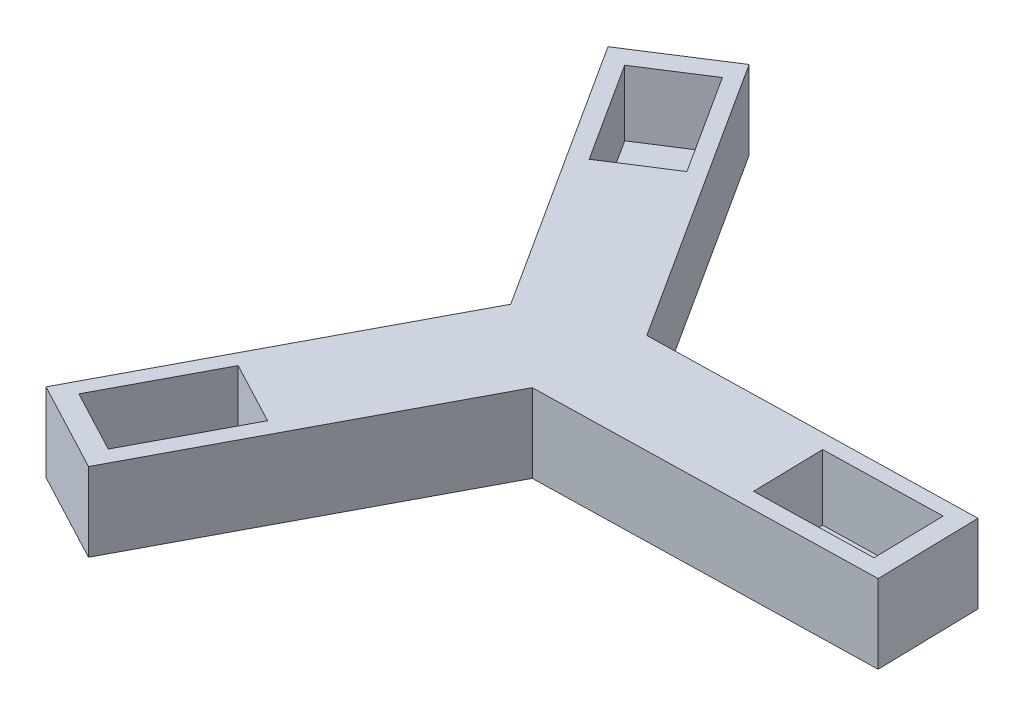
SolidWorks part; units mm, degrees
ref_plane "Front Plane" through (0, 0, 0) normal (0, 0, 1) x (1, 0, 0)
ref_plane "Top Plane" through (0, 0, 0) normal (0, 1, 0) x (1, 0, 0)
ref_plane "Right Plane" through (0, 0, 0) normal (1, 0, 0) x (0, 0, -1)
sketch "Sketch2" plane through (0, 0, 0) normal (0, 1, 0) x (1, 0, 0)
  line L1 (-129.6446, 105.7754) -> (170.3554, 105.7754)
  line L2 (-129.6446, 105.7754) -> (-129.6446, -194.2246)
  line L3 (-129.6446, -194.2246) -> (170.3554, -194.2246)
  line L4 (170.3554, 105.7754) -> (170.3554, -194.2246)
  dimension "D1" = 300
  dimension "D2" = 300
extrude "Boss-Extrude1" add sketch "Sketch2" along normal blind 10
sketch "Sketch7" plane through (0, 10, 0) normal (0, 1, 0) x (1, 0, 0)
  line L0 (-52.501, 16.4051) -> (-76.8122, 54.2728)
  line L1 (-76.8122, 54.2728) -> (-54.0916, 68.8596)
  line L2 (-52.501, 16.4051) -> (-29.7804, 30.9918)
  line L3 (-29.7804, 30.9918) -> (-54.0916, 68.8596)
  line L4 (-27.4397, -131.4548) -> (-48.4871, -171.2293)
  line L5 (-48.4871, -171.2293) -> (-72.3517, -158.6008)
  line L6 (-27.4397, -131.4548) -> (-51.3043, -118.8264)
  line L7 (-51.3043, -118.8264) -> (-72.3517, -158.6008)
  line L8 (88.0574, -35.0183) -> (133.046, -34.0062)
  line L9 (133.046, -34.0062) -> (133.6532, -60.9994)
  line L10 (88.0574, -35.0183) -> (88.6646, -62.0115)
  line L11 (88.6646, -62.0115) -> (133.6532, -60.9994)
  line L12 (-80.9419, -162.5405) -> (-52.8787, -109.5079)
  line L13 (-52.8787, -109.5079) -> (-18.4075, -127.749)
  line L14 (-18.4075, -127.749) -> (-46.4708, -180.7816)
  line L15 (-46.4708, -180.7816) -> (-80.9419, -162.5405)
  line L16 (80.4297, -29.4286) -> (140.4297, -28.0787)
  line L17 (140.4297, -28.0787) -> (141.3071, -67.0787)
  line L18 (141.3071, -67.0787) -> (81.3071, -68.4286)
  line L19 (81.3071, -68.4286) -> (80.4297, -29.4286)
  line L20 (-86.1235, 57.2076) -> (-53.3048, 78.2773)
  line L21 (-53.3048, 78.2773) -> (-20.8899, 27.787)
  line L22 (-20.8899, 27.787) -> (-53.7086, 6.7173)
  line L23 (-53.7086, 6.7173) -> (-86.1235, 57.2076)
  line L24 (-52.8787, -109.5079) -> (-19.5396, -46.5052)
  line L25 (-18.4075, -127.749) -> (12.1599, -69.9841)
  line L26 (-53.7086, 6.7173) -> (-19.5396, -46.5052)
  line L27 (-20.8899, 27.787) -> (16.7623, -30.8609)
  line L28 (80.4297, -29.4286) -> (16.7623, -30.8609)
  line L29 (81.3071, -68.4286) -> (12.1599, -69.9841)
  dimension "D1" = 27
  dimension "D2" = 60
  dimension "D3" = 39
  dimension "D4" = 6.25
  dimension "D5" = 7.5
  dimension "D6" = 60
  dimension "D7" = 39
  dimension "D8" = 6.25
  dimension "D9" = 7.5
  dimension "D10" = 60
  dimension "D11" = 39
  dimension "D12" = 6.25
  dimension "D13" = 7.5
  dimension "D14" = 180
  dimension "D15" = 180
  dimension "D16" = 180
extrude "Boss-Extrude3" add sketch "Sketch7" along normal blind 30 contours L19 L18 L17 L16 L11 L10 L8 L9 | L15 L14 L13 L12 L7 L6 L4 L5 | L23 L22 L21 L20 L3 L2 L0 L1 | L29 L19 L28 L27 L22 L26 L24 L13 L25 region at (-66.0723, 10, 136.4677) region at (2.7137, 10, 49.8877) region at (-69.1012, 10, -32.4855) region at (81.5986, 10, 48.9121)
extrude "Cut-Extrude1" cut sketch "Sketch2<2>" along normal blind 10
sketch "Sketch2<2>" plane through (0, 0, 0) normal (0, 1, 0) x (1, 0, 0) same geometry as "Sketch2"
extrude "Boss-Extrude4" add sketch "Sketch7<3>" along normal blind 5 contours L6 L7 L5 L4 | L2 L3 L1 L0 | L10 L11 L9 L8 region at (-53.2963, 10, -42.6323) region at (-49.8957, 10, 145.0278) region at (110.8553, 10, 48.0088)
sketch "Sketch7<3>" plane through (0, 10, 0) normal (0, 1, 0) x (1, 0, 0) same geometry as "Sketch7"
